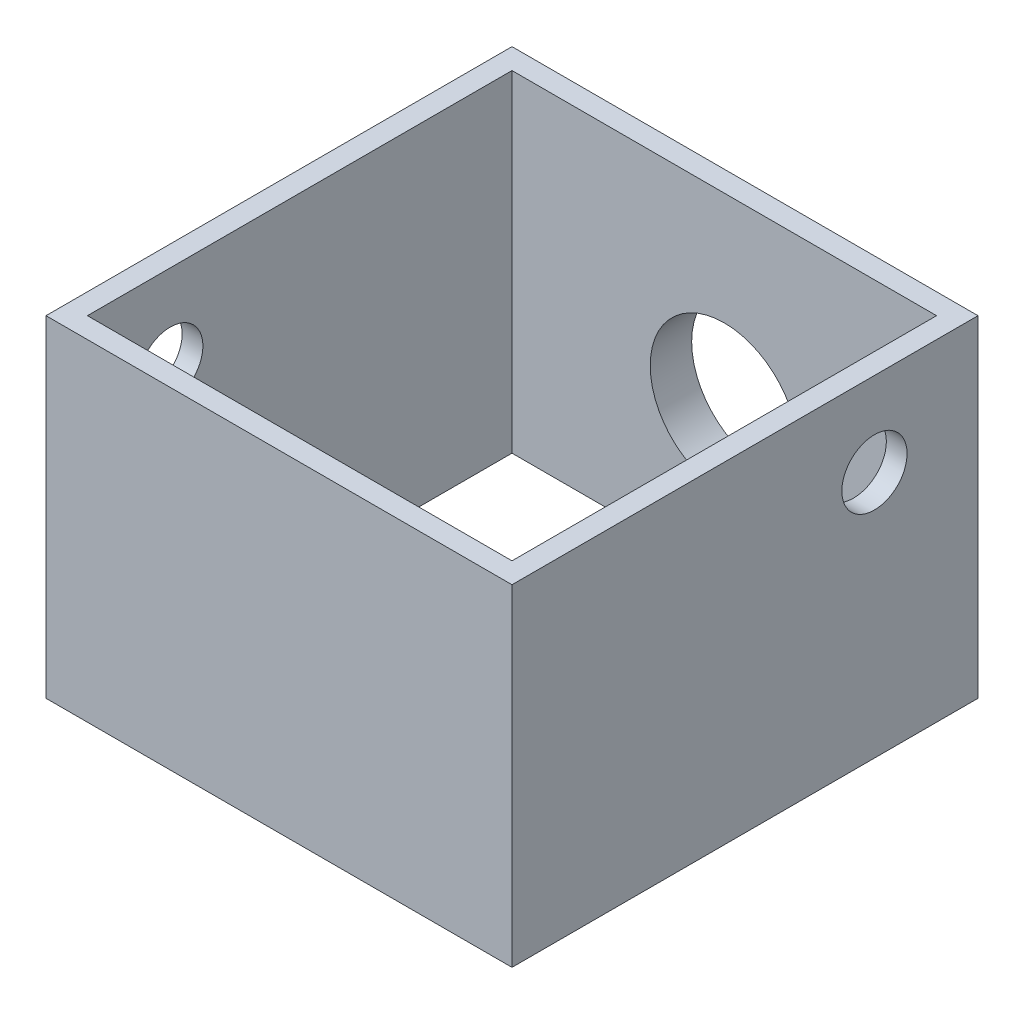
SolidWorks part; units mm, degrees
ref_plane "Front Plane" through (0, 0, 0) normal (0, 0, 1) x (1, 0, 0)
ref_plane "Top Plane" through (0, 0, 0) normal (0, 1, 0) x (1, 0, 0)
ref_plane "Right Plane" through (0, 0, 0) normal (1, 0, 0) x (0, 0, -1)
sketch "Sketch1" plane through (0, 0, 0) normal (0, 1, 0) x (1, 0, 0)
  line L1 (90, 100) -> (-135, 100)
  line L2 (90, 100) -> (90, -125)
  line L3 (90, -125) -> (-135, -125)
  line L4 (-135, 100) -> (-135, -125)
  line L7 (80, 90) -> (-125, 90)
  line L8 (80, 90) -> (80, -115)
  line L9 (80, -115) -> (-125, -115)
  line L10 (-125, 90) -> (-125, -115)
  point P0 (0, 0)
  point P6 (0, 0)
  dimension "D4" = 10
  dimension "D1" = 225
  dimension "D2" = 225
  dimension "D3" = 10
  dimension "D5" = 10
extrude "Walls" add sketch "Sketch1" along normal blind 160 contours L1 L4 L3 L2 L10 L7 L8 L9 region at (86.818, 0, 12.5)
extrude "Boss-Extrude2" add sketch "Sketch1<5>" along normal blind 7 contours L7 L10 L9 L8 region at (-22.5, 0, 12.5)
sketch "Sketch1<5>" plane through (0, 0, 0) normal (0, 1, 0) x (1, 0, 0) same geometry as "Sketch1"
sketch "Sketch2" plane through (0, 0, -100) normal (0, 0, -1) x (-1, 0, 0)
  circle A0 centre (22.5, 70) radius 35.75
  dimension "D1" = 70
  dimension "D2" = 71.5
extrude "Cut-Extrude1" cut sketch "Sketch2" against normal blind 197
sketch "Sketch6" plane through (0, 0, 115) normal (0, 0, -1) x (-1, 0, 0)
  circle A0 centre (22.5, 70) radius 35.75
  circle A1 centre (22.5, 70) radius 50
  dimension "D1" = 100
  dimension "D2" = 71.5
extrude "Boss-Extrude3" add sketch "Sketch6" along normal blind 14
sketch "Sketch7" plane through (0, 0, -100) normal (0, 0, -1) x (-1, 0, 0)
  circle A0 centre (22.5, 70) radius 35.75
  circle A1 centre (22.5, 70) radius 50
  dimension "D1" = 100
  dimension "D2" = 71.5
extrude "Boss-Extrude4" add sketch "Sketch7" along normal blind 10
sketch "Sketch9" plane through (0, 7, 0) normal (0, 1, 0) x (1, 0, 0)
  line L1 (-125, 90) -> (80, 90)
  line L2 (-125, 90) -> (-125, -115)
  line L3 (-125, -115) -> (80, -115)
  line L4 (80, 90) -> (80, -115)
extrude "Cut-Extrude4" cut sketch "Sketch9" against normal blind 10
sketch "Sketch10" plane through (-135, 0, 0) normal (-1, 0, 0) x (0, 0, 1)
  line L0 (134.6368, 0) -> (-114.8027, 0) construction
  line L1 (125, 169.2762) -> (125, -13.1048) construction
  line L2 (75, -13.1048) -> (75, 169.2762) construction
  line L3 (134.6368, 119.5) -> (-136.0526, 119.5) construction
  circle A1 centre (75, 119.5) radius 15.75
  dimension "D3" = 31.5
  dimension "D1" = 50
  dimension "D2" = 119.5
extrude "Cut-Extrude6" cut sketch "Sketch10" against normal blind 10
sketch "Sketch11" plane through (90, 0, 0) normal (1, 0, 0) x (0, 0, -1)
  line L0 (110.2103, 0) -> (-139.2292, 0) construction
  line L1 (50, 0) -> (50, 178.1806) construction
  line L2 (110.2103, 119.5) -> (0, 119.5) construction
  circle A0 centre (50, 119.5) radius 15.75
  dimension "D3" = 31.5
  dimension "D1" = 119.5
  dimension "D2" = 50
extrude "Cut-Extrude7" cut sketch "Sketch11" against normal blind 10
equation "\"hight\"=110"
